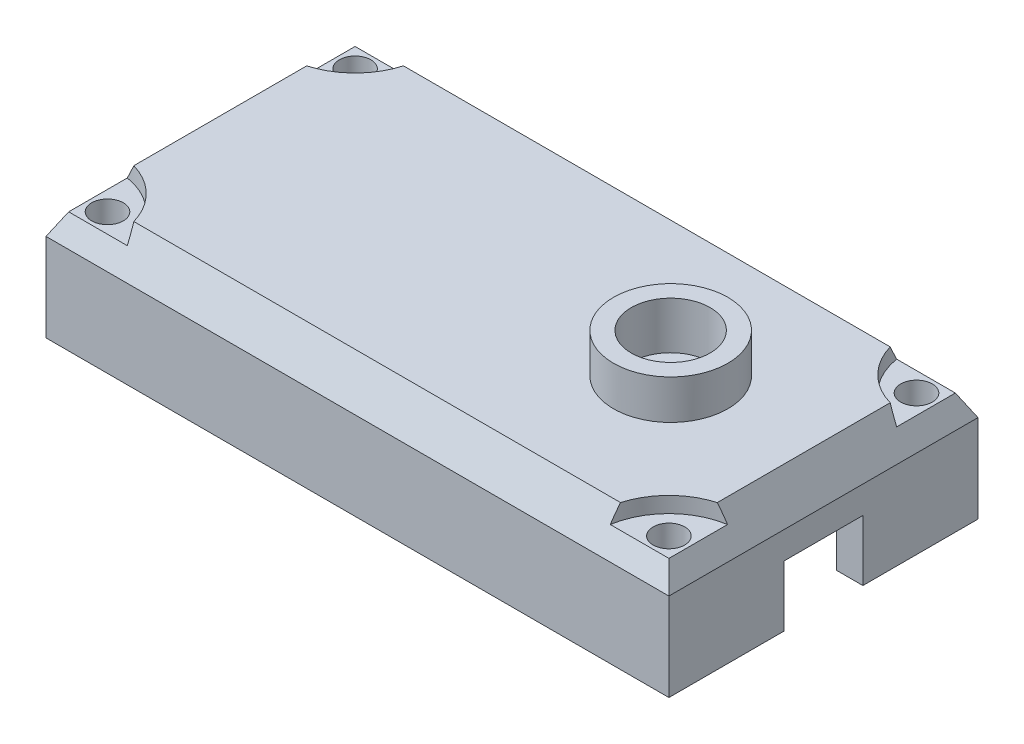
SolidWorks part; units mm, degrees
ref_plane "Front Plane" through (0, 0, 0) normal (0, 0, 1) x (1, 0, 0)
ref_plane "Top Plane" through (0, 0, 0) normal (0, 1, 0) x (1, 0, 0)
ref_plane "Right Plane" through (0, 0, 0) normal (1, 0, 0) x (0, 0, -1)
sketch "Sketch1" plane through (0, 0, 0) normal (0, 1, 0) x (1, 0, 0)
  line L1 (20.066, 9.9568) -> (-20.066, 9.9568)
  line L2 (20.066, 9.9568) -> (20.066, -9.9568)
  line L3 (20.066, -9.9568) -> (-20.066, -9.9568)
  line L4 (-20.066, 9.9568) -> (-20.066, -9.9568)
  line L5 (20.066, 9.9568) -> (-20.066, -9.9568) construction
  line L6 (20.066, -9.9568) -> (-20.066, 9.9568) construction
  point P0 (0, 0)
  dimension "D1" = 19.9136
  dimension "D2" = 40.132
extrude "Boss-Extrude1" add sketch "Sketch1" along normal blind 8.7122
shell "Shell1" thickness 1.7145 removed face at (0, 0, 0)
ref_plane "Plane2" through (0, 0, 0) normal (0, -1, 0) x (-1, 0, 0)
sketch "Sketch8" plane through (0, 0, 0) normal (0, -1, 0) x (-1, 0, 0)
  line L0 (0, -13.0536) -> (0, 17.6708) construction
  line L1 (27.4553, 0) -> (-28.1412, 0) construction
  line L2 (-20.066, 9.9568) -> (20.066, 9.9568) construction
  line L4 (20.066, 9.9568) -> (20.066, -9.9568) construction
  circle A0 centre (18.288, 8.1788) radius 1.778
  circle A1 centre (-18.288, 8.1788) radius 1.778
  circle A2 centre (18.288, -8.1788) radius 1.778
  circle A3 centre (-18.288, -8.1788) radius 1.778
sketch "Sketch2" plane through (0, 8.7122, 0) normal (0, 1, 0) x (1, 0, 0)
  line L1 (0, 15.3928) -> (0, -13.8045) construction
  line L2 (26.7949, 0) -> (-27.5388, 0) construction
  circle A0 centre (20.066, 9.9568) radius 4.5674
  circle A1 centre (-20.066, 9.9568) radius 4.5674
  circle A2 centre (-20.066, -9.9568) radius 4.5674
  circle A3 centre (20.066, -9.9568) radius 4.5674
sketch "Sketch3" plane through (0, 8.7122, 0) normal (0, 1, 0) x (1, 0, 0)
  line L1 (20.066, -9.9568) -> (20.066, 9.9568) construction
  circle A0 centre (10.2235, 0) radius 3.683
  dimension "D2" = 7.366
  dimension "D1" = 9.8425
extrude "Boss-Extrude2" add sketch "Sketch3" along normal blind 2.54
sketch "Sketch4" plane through (0, 11.2522, 0) normal (0, 1, 0) x (1, 0, 0)
  circle A0 centre (10.2235, 0) radius 2.54
  dimension "D1" = 5.08
extrude "Cut-Extrude2" cut sketch "Sketch4" against normal blind 3.048
extrude "Boss-Extrude5" add sketch "Sketch8" against normal up to surface (6.9977 mm away) up to face at (0, 6.9977, 0)
sketch "Sketch7" plane through (0, 0, 0) normal (0, -1, 0) x (-1, 0, 0)
  line L0 (0, -16.1532) -> (0, 17.3006) construction
  line L1 (28.752, 0) -> (-28.1196, 0) construction
  line L2 (-20.066, 9.9568) -> (20.066, 9.9568) construction
  line L3 (20.066, 9.9568) -> (20.066, -9.9568) construction
  circle A0 centre (18.0848, 7.9756) radius 1.016
  circle A1 centre (-18.0848, 7.9756) radius 1.016
  circle A2 centre (18.0848, -7.9756) radius 1.016
  circle A3 centre (-18.0848, -7.9756) radius 1.016
  dimension "D1" = 2.032
  dimension "D2" = 1.9812
  dimension "D3" = 1.9812
extrude "Cut-Extrude5" cut sketch "Sketch7" against normal up to surface (8.7122 mm away) up to face at (10.2235, 8.7122, -3.683)
chamfer "Chamfer1" distance 2.3876 distance2 1.27 4 edges at (20.066, 8.7122, 0) (0, 8.7122, -9.9568) (-20.066, 8.7122, 0) (0, 8.7122, 9.9568) first distance on face at (20.066, 4.3561, 0) first distance on face at (0, 4.3561, -9.9568) first distance on face at (-20.066, 4.3561, 0) first distance on face at (0, 4.3561, 9.9568)
extrude "Cut-Extrude6" cut sketch "Sketch2" against normal blind 1.016
sketch "Sketch10" plane through (0, 0, 0) normal (0, -1, 0) x (-1, 0, 0)
  line L5 (19.6402, -9.337) -> (-19.6402, 9.337) construction
  line L6 (19.7672, 0) -> (-19.6402, 0) construction
  line L7 (20.193, -9.9568) -> (-20.066, -9.9568)
  line L8 (20.193, -9.9568) -> (20.193, 9.9568)
  line L9 (20.193, 9.9568) -> (-20.066, 9.9568)
  line L10 (-20.066, -9.9568) -> (-20.066, 9.9568)
  line L11 (20.193, -9.9568) -> (-20.066, 9.9568) construction
  line L12 (20.193, 9.9568) -> (-20.066, -9.9568) construction
  point P0 (0, 0)
  point P6 (0.0635, 0)
extrude "Cut-Extrude7" cut sketch "Sketch10" against normal blind 0.6604
sketch "Sketch11" plane through (20.066, 0, 0) normal (1, 0, 0) x (0, 0, -1)
  line L0 (0, -2.5512) -> (0, 13.0859) construction
  line L1 (-55, 0) -> (55, 0) construction
  line L2 (-2.54, 4.572) -> (2.54, 4.572)
  line L3 (-2.54, 4.572) -> (-2.54, 0)
  line L4 (-2.54, 0) -> (2.54, 0)
  line L5 (2.54, 4.572) -> (2.54, 0)
  line L6 (-2.54, 4.572) -> (2.54, 0) construction
  line L7 (-2.54, 0) -> (2.54, 4.572) construction
  point P3 (0, 2.286)
  dimension "D1" = 5.08
  dimension "D2" = 4.572
extrude "Cut-Extrude8" cut sketch "Sketch11" against normal up to surface (1.7145 mm away) up to face at (18.3515, 3.8291, 0)
sketch "Sketch12" plane through (0, 0, 0) normal (0, -1, 0) x (-1, 0, 0)
  line L0 (-25.0797, 0) -> (28.5864, 0) construction
  line L1 (6.3572, -8.5725) -> (12.4234, -8.5725) construction
  line L4 (18.8722, 1.9377) -> (18.8722, -1.9346) construction
  circle A0 centre (10.2997, 0) radius 8.5725
  dimension "D1" = 17.145
extrude "Cut-Extrude9" cut sketch "Sketch12" against normal up to surface (6.9977 mm away) up to face at (0, 6.9977, 0)
